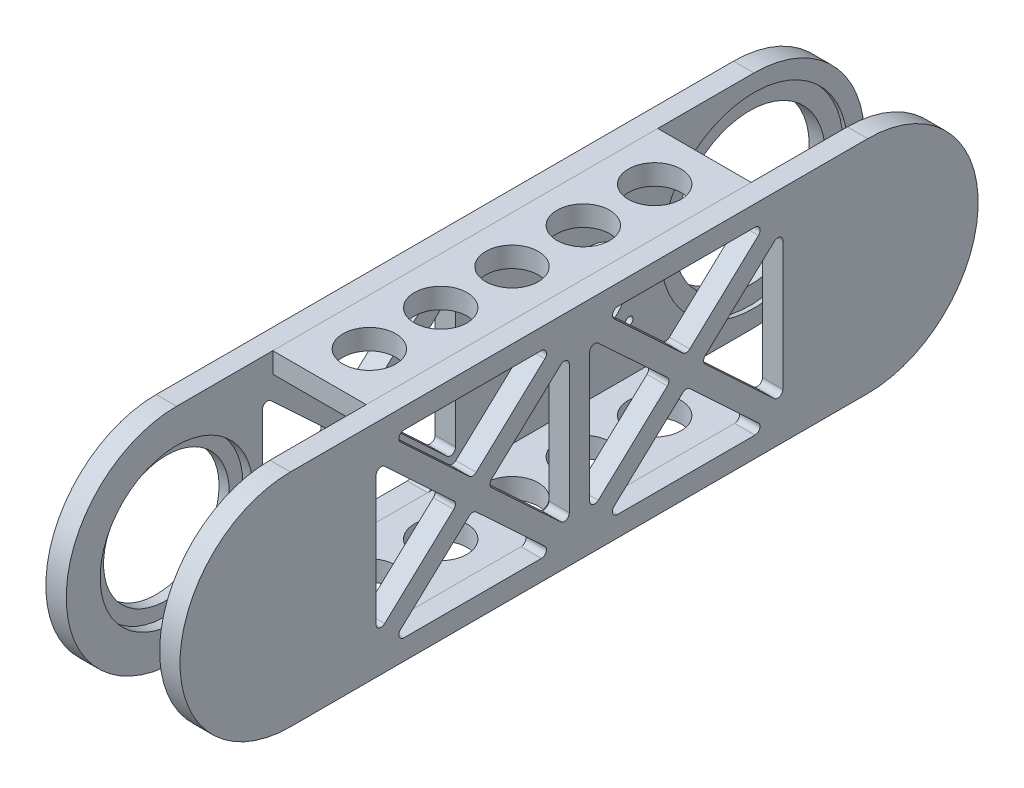
SolidWorks part; units mm, degrees
note: '?' marks a value the reader was unsure of. The reader was unsure of these and kept them because the rebuilt part matched: shared geometry of "Plate_refs<4>", "Plate_refs<5>", "Sketch2<3>", "Plate_refs<6>", "Plate_refs<7>".
other "Side_plate_motors"
other "Top_plate"
other "Bottom_plate"
other "Side_plate_idle" parameters "D1"=24.6013, "D3"=35.4921, "D4"=126.5518, "D5"=107.9106, "D6"=30, "D7"=70, "D8"=80, "D9"=80.6949, "D10"=110, "D2"=256.099
material "6061 Alloy"
ref_plane "Front Plane" through (0, 0, 0) normal (1, 0, 0) x (0, 1, 0)
ref_plane "Top Plane" through (0, 0, 0) normal (0, 0, 1) x (0, 1, 0)
ref_plane "Right Plane" through (0, 0, 0) normal (0, 1, 0) x (-1, 0, 0)
ref_axis "Axis1" through (0, -88.99, 0) along (0, 1, 0)?
ref_axis "Axis2" through (55, 0, 0) along (-1, 0, 0)?
sketch "Plate_refs" plane through (0, 0, 0) normal (1, 0, 0) x (0, 1, 0)
  line L0 (0, 0) -> (0, 340) construction
  line L1 (0, -55) -> (0, 55) construction
  line L2 (-65, 340) -> (-65, 0)
  line L3 (65, 340) -> (65, 0)
  circle A0 centre (0, 0) radius 44.5
  circle A1 centre (0, 340) radius 15
  arc A2 (-65, 0) -> (65, 0) centre (0, 0) ccw
  arc A3 (65, 340) -> (-65, 340) centre (0, 340) ccw
  circle A4 centre (0, 0) radius 15
  arc A5 (-65, 340) -> (0, 275) centre (0, 340) ccw construction
  arc A6 (0, 275) -> (65, 340) centre (0, 340) ccw construction
  arc A7 (0, 65) -> (-65, 0) centre (0, 0) ccw construction
  arc A8 (65, 0) -> (0, 65) centre (0, 0) ccw construction
  circle A9 centre (0, 340) radius 35 construction
  circle A10 centre (0, 340) radius 37
  circle A11 centre (0, 340) radius 45
  circle A12 centre (0, 0) radius 55
  dimension "D1" = 89
  dimension "D3" = 30
  dimension "D4" = 130
  dimension "D5" = 130
  dimension "D9" = 90
  dimension "D2" = 340
  dimension "D8" = 2
extrude "Plate_shape" add sketch "Plate_refs" along normal blind 12 contours L3 A3 L2 A2 A0 A1 | A11 A10 | A10 A1 | A12 A0
extrude "Shoulder_gear_slot" cut sketch "Plate_refs<4>" against normal blind 2.5 from surface at 12 contours A0 | A12 starting at face at (12, 0, 170)
sketch "Plate_refs<4>" plane through (0, 0, 0) normal (1, 0, 0) x (0, 1, 0) same geometry as "Plate_refs"
extrude "Elbow_gear_slot" cut sketch "Plate_refs<5>" against normal blind 6 from surface at 12 contours A11 starting at face at (12, 0, -55)
sketch "Plate_refs<5>" plane through (0, 0, 0) normal (1, 0, 0) x (0, 1, 0) same geometry as "Plate_refs"
sketch "Sketch1" plane through (12, 0, 0) normal (1, 0, 0) x (0, 1, 0)
  circle A0 centre (0, 340) radius 42 construction
  circle A1 centre (-42, 340) radius 2.5
  circle A2 centre (0, 382) radius 2.5
  circle A3 centre (42, 340) radius 2.5
  circle A4 centre (0, 298) radius 2.5
  dimension "D1" = 84
  dimension "D2" = 5
  dimension "D3" = 4
extrude "Elbow_joint_screw_relief" [suppressed] cut sketch "Sketch1" against normal through all both and the other way through all
sketch "Sketch2" plane through (0, 0, 0) normal (-1, 0, 0) x (0, -1, 0)
  line L0 (0, 43.45) -> (0, -43.45) construction
  line L1 (-30, 128.2478) -> (30, 128.2478) construction
  line L2 (-30, 128.2478) -> (-30, 68.2478) construction
  line L3 (-30, 68.2478) -> (30, 68.2478) construction
  line L4 (30, 128.2478) -> (30, 68.2478) construction
  line L5 (-30, 128.2478) -> (30, 68.2478) construction
  line L6 (-30, 68.2478) -> (30, 128.2478) construction
  line L8 (-35, 133.2478) -> (35, 133.2478)
  line L9 (-35, 133.2478) -> (-35, 63.2478)
  line L10 (-35, 63.2478) -> (35, 63.2478)
  line L11 (35, 133.2478) -> (35, 63.2478)
  line L12 (-35, 133.2478) -> (35, 63.2478) construction
  line L13 (-35, 63.2478) -> (35, 133.2478) construction
  circle A0 centre (0, 98.2478) radius 25
  circle A1 centre (0, 98.2478) radius 35 construction
  circle A2 centre (24.7487, 122.9966) radius 2.25
  circle A3 centre (24.7487, 73.4991) radius 2.25
  circle A4 centre (-24.7487, 73.4991) radius 2.25
  circle A5 centre (-24.7487, 122.9966) radius 2.25
  point P0 (0, 98.2478)
  dimension "D2" = 50
  dimension "D3" = 70
  dimension "D5" = 4.5
  dimension "D1" = 60
  dimension "D4" = 70
  dimension "D6" = 4
extrude "J3_motor_1" cut sketch "Sketch2" against normal through all both and the other way through all contours A0 | A5 | A3 | A2 | A4
extrude "J3_motor_2" cut sketch "Sketch2<3>" against normal blind 6 and the other way through all
sketch "Sketch2<3>" plane through (0, 0, 0) normal (-1, 0, 0) x (0, -1, 0) same geometry as "Sketch2"
fillet "Fillet1" radius 6 4 edges at (3, -35, 63.2478) (3, -35, 133.2478) (3, 35, 133.2478) (3, 35, 63.2478)
sketch "Sketch3" plane through (0, 0, 0) normal (1, 0, 0) x (0, 1, 0)
  line L0 (-65, 170) -> (0, 170) construction
  line L1 (-65, 340) -> (-65, 0) construction
  line L2 (0, -43.45) -> (0, 43.45) construction
  line L3 (-65, 56.6667) -> (-53, 56.6667)
  line L4 (-65, 170) -> (-53, 170) construction
  line L5 (-65, 56.6667) -> (-65, 283.3333)
  line L6 (-65, 283.3333) -> (-53, 283.3333)
  line L7 (-53, 56.6667) -> (-53, 283.3333)
  line L8 (-65, 170) -> (-53, 283.3333) construction
  line L9 (-65, 283.3333) -> (-53, 170) construction
  point P9 (-59, 226.6667)
  dimension "D1" = 113.3333
  dimension "D2" = 12
extrude "Top_plate" add sketch "Sketch3" along normal blind 55 from surface at 12 separate body starting at face at (12, 24.7487, 125.2466)
mirror "Bottom_plate" about plane through (0, 0, 0) normal (0, 1, 0) of bodies 108
extrude "Side_plate_2" add sketch "Plate_refs<6>" along normal blind 12 from surface at 67 separate body contours L2 A2 L3 A3 starting at face at (67, -59, 170)
sketch "Plate_refs<6>" plane through (0, 0, 0) normal (1, 0, 0) x (0, 1, 0) same geometry as "Plate_refs"
sketch "Sketch4" plane through (67, 0, 0) normal (-1, 0, 0) x (0, -1, 0)
  line L2 (65, 0) -> (65, 340)
  line L3 (-65, 340) -> (-65, 0)
  line L4 (65, 0) -> (65, 340)
  line L5 (-65, 340) -> (-65, 0)
  circle A0 centre (0, 340) radius 15 construction
  circle A1 centre (0, 340) radius 15 construction
  arc A2 (-65, 0) -> (65, 0) centre (0, 0) ccw
  arc A3 (65, 340) -> (-65, 340) centre (0, 340) ccw
  arc A4 (-65, 0) -> (65, 0) centre (0, 0) ccw
  arc A5 (65, 340) -> (-65, 340) centre (0, 340) ccw
  circle A7 centre (0, 0) radius 15 construction
  circle A8 centre (0, 340) radius 14
  circle A9 centre (0, 0) radius 14
  dimension "D2" = 28
  dimension "D3" = 28
extrude "Side_plate_bearing_mounts" cut sketch "Sketch4" against normal blind 8 contours A8 | A9
extrude "Cut-Extrude3" cut sketch "Plate_refs<7>" along normal blind 8 contours A10
sketch "Plate_refs<7>" plane through (0, 0, 0) normal (1, 0, 0) x (0, 1, 0) same geometry as "Plate_refs"
sketch "Sketch5" plane through (0, 0, 0) normal (-1, 0, 0) x (0, -1, 0)
  line L0 (0, 340) -> (0, 241.4496) construction
  line L1 (43.45, 0) -> (-43.45, 0) construction
  line L2 (-53, 50) -> (53, 50) construction
  line L3 (-53, 50) -> (-53, 289.5307) construction
  line L4 (-53, 289.5307) -> (53, 289.5307) construction
  line L5 (53, 50) -> (53, 289.5307) construction
  line L6 (-53, 50) -> (53, 289.5307) construction
  line L7 (-53, 289.5307) -> (53, 50) construction
  line L8 (65, 340) -> (65, 0) construction
  line L9 (0, 170) -> (0, 223.8465) construction
  line L10 (-40.0985, 180.8104) -> (-2.1949, 221.4907)
  line L11 (-53, 175.7654) -> (53, 175.7654) construction
  line L12 (-53, 175.7654) -> (-53, 289.5307) construction
  line L13 (-53, 289.5307) -> (53, 289.5307) construction
  line L14 (53, 175.7654) -> (53, 289.5307) construction
  line L15 (-53, 175.7654) -> (-18.8668, 212.3991) construction
  line L16 (-53, 289.5307) -> (-4.1004, 237.0488) construction
  line L17 (-47.8051, 190.1424) -> (-21.5075, 218.3665)
  line L18 (-40.0985, 284.4856) -> (-2.1949, 243.8053)
  line L19 (40.0985, 180.8104) -> (2.1949, 221.4907)
  line L20 (-37.9036, 175.7654) -> (37.9036, 175.7654)
  line L21 (53, 192.1875) -> (53, 273.1086)
  line L22 (-37.9036, 289.5307) -> (37.9036, 289.5307)
  line L23 (-53, 273.1086) -> (-53, 192.1875)
  line L24 (-8.2008, 232.648) -> (-4.1004, 237.0488) construction
  line L25 (2.1949, 243.8053) -> (40.0985, 284.4856)
  line L26 (-4.1004, 237.0488) -> (0, 232.648) construction
  line L27 (0, 232.648) -> (4.1004, 228.2472) construction
  line L28 (-4.1004, 237.0488) -> (0, 241.4496) construction
  line L29 (0, 241.4496) -> (0, 232.648) construction
  line L30 (0, 223.8465) -> (0, 0) construction
  line L31 (0, 232.648) -> (0, 241.4496) construction
  line L32 (0, 241.4496) -> (0, 289.5307) construction
  line L33 (0, 241.4496) -> (4.1004, 237.0488) construction
  line L34 (10.1063, 230.6029) -> (47.8051, 190.1424)
  line L35 (4.1004, 237.0488) -> (53, 289.5307) construction
  line L36 (4.1004, 237.0488) -> (8.2008, 232.648) construction
  line L37 (4.1004, 228.2472) -> (8.2008, 232.648) construction
  line L38 (10.1063, 234.6931) -> (47.8051, 275.1537)
  line L39 (4.1004, 228.2472) -> (18.8668, 212.3991) construction
  line L40 (18.8668, 212.3991) -> (53, 175.7654) construction
  line L41 (0, 223.8465) -> (4.1004, 228.2472) construction
  line L42 (0, 223.8465) -> (0, 232.648) construction
  line L43 (0, 232.648) -> (0, 223.8465) construction
  line L44 (-4.1004, 228.2472) -> (0, 232.648) construction
  line L45 (0, 232.648) -> (4.1004, 237.0488) construction
  line L46 (-4.1004, 228.2472) -> (-8.2008, 232.648) construction
  line L47 (-10.1063, 234.6931) -> (-47.8051, 275.1537)
  line L48 (-21.5075, 218.3665) -> (-10.1063, 230.6029)
  line L49 (-18.8668, 212.3991) -> (-4.1004, 228.2472) construction
  line L50 (0, 223.8465) -> (-4.1004, 228.2472) construction
  line L51 (0, 169.7654) -> (53, 169.7654) construction
  line L52 (0, 115.6843) -> (-4.1004, 111.2835) construction
  line L53 (-18.8668, 127.1316) -> (-4.1004, 111.2835) construction
  line L54 (-4.1004, 111.2835) -> (-8.2008, 106.8827) construction
  line L55 (0, 106.8827) -> (4.1004, 102.4819) construction
  line L56 (-4.1004, 111.2835) -> (0, 106.8827) construction
  line L57 (0, 106.8827) -> (0, 115.6843) construction
  line L58 (0, 115.6843) -> (0, 106.8827) construction
  line L59 (0, 115.6843) -> (4.1004, 111.2835) construction
  line L60 (18.8668, 127.1316) -> (53, 163.7654) construction
  line L61 (4.1004, 111.2835) -> (18.8668, 127.1316) construction
  line L62 (4.1004, 111.2835) -> (8.2008, 106.8827) construction
  line L63 (4.1004, 102.4819) -> (8.2008, 106.8827) construction
  line L64 (4.1004, 102.4819) -> (53, 50) construction
  line L65 (0, 98.0811) -> (4.1004, 102.4819) construction
  line L66 (0, 98.0811) -> (0, 50) construction
  line L67 (0, 106.8827) -> (0, 98.0811) construction
  line L68 (0, 98.0811) -> (0, 106.8827) construction
  line L69 (-4.1004, 102.4819) -> (0, 98.0811) construction
  line L70 (0, 106.8827) -> (4.1004, 111.2835) construction
  line L71 (-4.1004, 102.4819) -> (0, 106.8827) construction
  line L72 (-8.2008, 106.8827) -> (-4.1004, 102.4819) construction
  line L73 (-53, 50) -> (-4.1004, 102.4819) construction
  line L74 (-53, 163.7654) -> (-18.8668, 127.1316) construction
  line L75 (53, 163.7654) -> (53, 50) construction
  line L76 (-53, 50) -> (53, 50) construction
  line L77 (-53, 163.7654) -> (-53, 50) construction
  line L78 (-53, 163.7654) -> (53, 163.7654) construction
  line L79 (-53, 50) -> (53, 50) construction
  line L80 (-21.5075, 121.1642) -> (-10.1063, 108.9278)
  line L81 (-10.1063, 104.8376) -> (-47.8051, 64.3771)
  line L82 (10.1063, 104.8376) -> (47.8051, 64.3771)
  line L83 (10.1063, 108.9278) -> (47.8051, 149.3883)
  line L84 (2.1949, 95.7254) -> (40.0985, 55.0451)
  line L85 (-53, 66.4221) -> (-53, 147.3432)
  line L86 (-37.9036, 50) -> (37.9036, 50)
  line L87 (53, 147.3432) -> (53, 66.4221)
  line L88 (-37.9036, 163.7654) -> (37.9036, 163.7654)
  line L89 (40.0985, 158.7203) -> (2.1949, 118.04)
  line L90 (-40.0985, 55.0451) -> (-2.1949, 95.7254)
  line L91 (-47.8051, 149.3883) -> (-21.5075, 121.1642)
  line L92 (-40.0985, 158.7203) -> (-2.1949, 118.04)
  arc A0 (-40.0985, 180.8104) -> (-37.9036, 175.7654) centre (-37.9036, 178.7654) ccw
  arc A1 (-2.1949, 221.4907) -> (2.1949, 221.4907) centre (0, 219.4457) cw
  arc A2 (40.0985, 180.8104) -> (37.9036, 175.7654) centre (37.9036, 178.7654) cw
  arc A3 (47.8051, 190.1424) -> (53, 192.1875) centre (50, 192.1875) ccw
  arc A4 (10.1063, 230.6029) -> (10.1063, 234.6931) centre (12.3012, 232.648) cw
  arc A5 (47.8051, 275.1537) -> (53, 273.1086) centre (50, 273.1086) cw
  arc A6 (40.0985, 284.4856) -> (37.9036, 289.5307) centre (37.9036, 286.5307) ccw
  arc A7 (-40.0985, 284.4856) -> (-37.9036, 289.5307) centre (-37.9036, 286.5307) cw
  arc A8 (2.1949, 243.8053) -> (-2.1949, 243.8053) centre (0, 245.8504) cw
  arc A9 (-10.1063, 230.6029) -> (-10.1063, 234.6931) centre (-12.3012, 232.648) ccw
  arc A10 (-47.8051, 190.1424) -> (-53, 192.1875) centre (-50, 192.1875) cw
  arc A11 (-47.8051, 275.1537) -> (-53, 273.1086) centre (-50, 273.1086) ccw
  arc A12 (-47.8051, 64.3771) -> (-53, 66.4221) centre (-50, 66.4221) cw
  arc A13 (-47.8051, 149.3883) -> (-53, 147.3432) centre (-50, 147.3432) ccw
  arc A14 (-10.1063, 108.9278) -> (-10.1063, 104.8376) centre (-12.3012, 106.8827) cw
  arc A15 (2.1949, 95.7254) -> (-2.1949, 95.7254) centre (0, 93.6803) ccw
  arc A16 (-40.0985, 55.0451) -> (-37.9036, 50) centre (-37.9036, 53) ccw
  arc A17 (40.0985, 55.0451) -> (37.9036, 50) centre (37.9036, 53) cw
  arc A18 (47.8051, 64.3771) -> (53, 66.4221) centre (50, 66.4221) ccw
  arc A19 (10.1063, 108.9278) -> (10.1063, 104.8376) centre (12.3012, 106.8827) ccw
  arc A20 (47.8051, 149.3883) -> (53, 147.3432) centre (50, 147.3432) cw
  arc A21 (40.0985, 158.7203) -> (37.9036, 163.7654) centre (37.9036, 160.7654) ccw
  arc A22 (-2.1949, 118.04) -> (2.1949, 118.04) centre (0, 120.085) ccw
  arc A23 (-40.0985, 158.7203) -> (-37.9036, 163.7654) centre (-37.9036, 160.7654) cw
  point P4 (0, 169.7654)
  point P15 (0, 232.648)
  point P41 (-44.7992, 175.7654)
  point P47 (44.7992, 175.7654)
  point P50 (53, 184.5669)
  point P56 (53, 280.7291)
  point P59 (44.7992, 289.5307)
  point P62 (-44.7992, 289.5307)
  point P71 (-53, 184.5669)
  point P74 (-53, 280.7291)
  point P128 (-53, 58.8016)
  point P129 (-53, 154.9638)
  point P130 (-44.7992, 50)
  point P131 (44.7992, 50)
  point P132 (53, 58.8016)
  point P133 (53, 154.9638)
  point P134 (44.7992, 163.7654)
  point P135 (-44.7992, 163.7654)
  point P136 (0, 106.8827)
  dimension "D5" = 3
  dimension "D1" = 50
  dimension "D2" = 12
  dimension "D3" = 6
  dimension "D4" = 6
  dimension "D6" = 6
extrude "Cut-Extrude4" cut sketch "Sketch5" against normal through all both and the other way through all contours L47 A11 L23 A10 L17 L48 A9 | A8 L25 A6 L22 A7 L18 | A5 L38 A4 L34 A3 L21 | A2 L19 A1 L10 A0 L20
sketch "Sketch7" plane through (79, 0, 0) normal (1, 0, 0) x (0, 1, 0)
  line L0 (10.1063, 104.8376) -> (47.8051, 64.3771) construction
  line L1 (53, 66.4221) -> (53, 147.3432) construction
  line L2 (47.8051, 149.3883) -> (21.5075, 121.1642) construction
  line L3 (21.5075, 121.1642) -> (10.1063, 108.9278) construction
  line L4 (37.9036, 50) -> (-37.9036, 50) construction
  line L5 (40.0985, 55.0451) -> (2.1949, 95.7254) construction
  line L6 (-2.1949, 95.7254) -> (-40.0985, 55.0451) construction
  line L7 (-10.1063, 104.8376) -> (-47.8051, 64.3771) construction
  line L8 (-53, 147.3432) -> (-53, 66.4221) construction
  line L9 (-10.1063, 108.9278) -> (-47.8051, 149.3883) construction
  line L10 (-40.0985, 158.7203) -> (-2.1949, 118.04) construction
  line L11 (37.9036, 163.7654) -> (-37.9036, 163.7654) construction
  line L12 (40.0985, 158.7203) -> (2.1949, 118.04) construction
  line L13 (10.1063, 104.8376) -> (47.8051, 64.3771)
  line L14 (53, 66.4221) -> (53, 147.3432)
  line L15 (47.8051, 149.3883) -> (21.5075, 121.1642)
  line L16 (21.5075, 121.1642) -> (10.1063, 108.9278)
  line L17 (37.9036, 50) -> (-37.9036, 50)
  line L18 (40.0985, 55.0451) -> (2.1949, 95.7254)
  line L19 (-2.1949, 95.7254) -> (-40.0985, 55.0451)
  line L20 (-10.1063, 104.8376) -> (-47.8051, 64.3771)
  line L21 (-53, 147.3432) -> (-53, 66.4221)
  line L22 (-10.1063, 108.9278) -> (-47.8051, 149.3883)
  line L23 (-40.0985, 158.7203) -> (-2.1949, 118.04)
  line L24 (37.9036, 163.7654) -> (-37.9036, 163.7654)
  line L25 (40.0985, 158.7203) -> (2.1949, 118.04)
  arc A0 (47.8051, 64.3771) -> (53, 66.4221) centre (50, 66.4221) ccw construction
  arc A1 (53, 147.3432) -> (47.8051, 149.3883) centre (50, 147.3432) ccw construction
  arc A2 (10.1063, 108.9278) -> (10.1063, 104.8376) centre (12.3012, 106.8827) ccw construction
  arc A3 (-40.0985, 55.0451) -> (-37.9036, 50) centre (-37.9036, 53) ccw construction
  arc A4 (37.9036, 50) -> (40.0985, 55.0451) centre (37.9036, 53) ccw construction
  arc A5 (2.1949, 95.7254) -> (-2.1949, 95.7254) centre (0, 93.6803) ccw construction
  arc A6 (-53, 66.4221) -> (-47.8051, 64.3771) centre (-50, 66.4221) ccw construction
  arc A7 (-47.8051, 149.3883) -> (-53, 147.3432) centre (-50, 147.3432) ccw construction
  arc A8 (-10.1063, 104.8376) -> (-10.1063, 108.9278) centre (-12.3012, 106.8827) ccw construction
  arc A9 (-2.1949, 118.04) -> (2.1949, 118.04) centre (0, 120.085) ccw construction
  arc A10 (-37.9036, 163.7654) -> (-40.0985, 158.7203) centre (-37.9036, 160.7654) ccw construction
  arc A11 (40.0985, 158.7203) -> (37.9036, 163.7654) centre (37.9036, 160.7654) ccw construction
  arc A12 (47.8051, 64.3771) -> (53, 66.4221) centre (50, 66.4221) ccw
  arc A13 (53, 147.3432) -> (47.8051, 149.3883) centre (50, 147.3432) ccw
  arc A14 (10.1063, 108.9278) -> (10.1063, 104.8376) centre (12.3012, 106.8827) ccw
  arc A15 (-40.0985, 55.0451) -> (-37.9036, 50) centre (-37.9036, 53) ccw
  arc A16 (37.9036, 50) -> (40.0985, 55.0451) centre (37.9036, 53) ccw
  arc A17 (2.1949, 95.7254) -> (-2.1949, 95.7254) centre (0, 93.6803) ccw
  arc A18 (-53, 66.4221) -> (-47.8051, 64.3771) centre (-50, 66.4221) ccw
  arc A19 (-47.8051, 149.3883) -> (-53, 147.3432) centre (-50, 147.3432) ccw
  arc A20 (-10.1063, 104.8376) -> (-10.1063, 108.9278) centre (-12.3012, 106.8827) ccw
  arc A21 (-2.1949, 118.04) -> (2.1949, 118.04) centre (0, 120.085) ccw
  arc A22 (-37.9036, 163.7654) -> (-40.0985, 158.7203) centre (-37.9036, 160.7654) ccw
  arc A23 (40.0985, 158.7203) -> (37.9036, 163.7654) centre (37.9036, 160.7654) ccw
extrude "Cut-Extrude5" cut sketch "Sketch7" against normal blind 20 and the other way through all
sketch "Sketch8" plane through (0, -65, 0) normal (0, -1, 0) x (1, 0, 0)
  line L0 (39.5, 283.3333) -> (39.5, 56.6667) construction
  line L1 (67, 283.3333) -> (12, 283.3333) construction
  line L2 (67, 56.6667) -> (12, 56.6667) construction
  line L3 (39.5, 170) -> (67, 170) construction
  line L4 (67, 340) -> (67, 0) construction
  circle A0 centre (39.5, 170) radius 15.5
  circle A1 centre (39.5, 128) radius 15.5
  circle A2 centre (39.5, 86) radius 15.5
  circle A3 centre (39.5, 254) radius 15.5
  circle A4 centre (39.5, 212) radius 15.5
  dimension "D1" = 31
  dimension "D2" = 3
extrude "Cut-Extrude6" cut sketch "Sketch8" against normal through all both and the other way through all
equation "\"j2_gear_output_out_d\"=89"
equation "\"j2_gear_output_h\"=6"
equation "\"link_lenght\"= 340"
equation "\"D1@Plate_refs\" = \"j2_gear_output_out_d\""
equation "\"D2@Plate_refs\" = \"link_lenght\""
equation "\"j3_elbow_input_bearing_d\"= 30"
equation "\"D3@Plate_refs\" = \"j3_elbow_input_bearing_d\""
equation "\"plate_thickness\"= 12"
equation "\"D1@Plate_shape\" = \"plate_thickness\""
equation "\"D1@Shoulder_gear_slot\" = \"j2_gear_output_h\""
equation "\"j3_gear_input_d\"= 90"
equation "\"j3_geat_output_d\"= 70"
equation "\"D7@Plate_refs\"=\"j3_geat_output_d\""
equation "\"D9@Plate_refs\"=\"j3_gear_input_d\""
equation "\"D1@Elbow_gear_slot\"=\"j2_gear_output_h\""
equation "\"D1@Sketch3\"=\"link_lenght\"/3"
equation "\"D2@Sketch3\"=\"plate_thickness\""
equation "\"D1@Side_plate_2\" = \"plate_thickness\""
equation "\"14mm_axle_bearing_out\"= 28"
equation "\"D2@Sketch4\"=\"14mm_axle_bearing_out\""
equation "\"D3@Sketch4\"=\"14mm_axle_bearing_out\""
